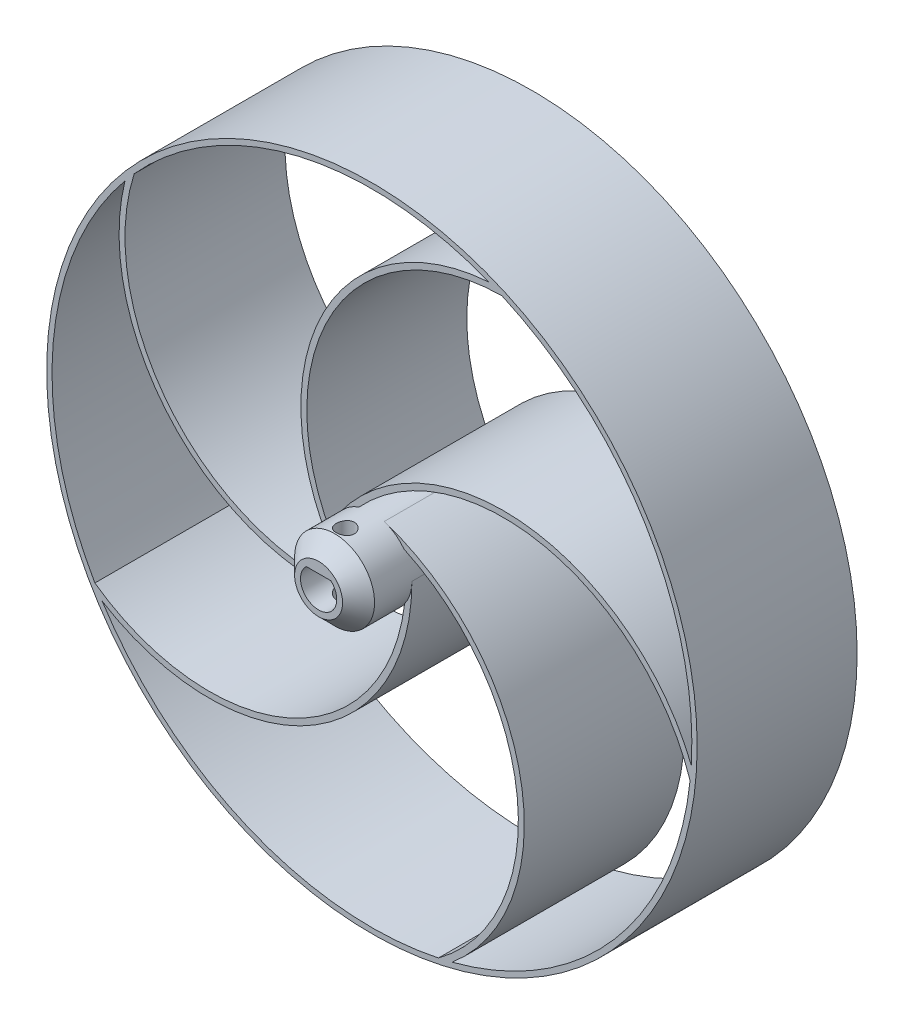
SolidWorks part; units mm, degrees
ref_plane "Front Plane" through (0, 0, 0) normal (0, 0, 1) x (1, 0, 0)
ref_plane "Top Plane" through (0, 0, 0) normal (0, 1, 0) x (1, 0, 0)
ref_plane "Right Plane" through (0, 0, 0) normal (1, 0, 0) x (0, 0, -1)
sketch "Sketch1" plane through (0, 0, 0) normal (0, 0, 1) x (1, 0, 0)
  line L0 (0, 0) -> (-30.5, 0) construction
  line L1 (-1.1522, 1.25) -> (1.1522, 1.25)
  circle A0 centre (0, 0) radius 30.5
  circle A1 centre (0, 0) radius 30
  circle A2 centre (0, 0) radius 3.75
  arc A3 (3.75, 0) -> (-25.2971, -16.1262) centre (-15.25, 0) cw
  arc A4 (3.0667, -2.1581) -> (-25.9804, -15.0007) centre (-15.25, 0) cw
  arc A5 (-1.1048, -3.5836) -> (-22.2949, 20.0734) centre (-4.7125, 14.5036) cw
  arc A6 (1.1588, -3.5665) -> (-23.1542, 19.0757) centre (-4.7125, 14.5036) cw
  arc A7 (-3.7496, -0.0566) -> (12.2014, 27.4067) centre (12.3375, 8.9637) cw
  arc A8 (-3.0338, -2.2042) -> (10.9871, 27.9157) centre (12.3375, 8.9637) cw
  arc A9 (-1.2125, 3.5486) -> (29.8357, -3.1351) centre (12.3375, -8.9637) cw
  arc A10 (-3.0338, 2.2042) -> (29.9446, -1.8229) centre (12.3375, -8.9637) cw
  arc A11 (3.0002, 2.2497) -> (6.2381, -29.3443) centre (-4.7125, -14.5036) cw
  arc A12 (1.1588, 3.5665) -> (7.5197, -29.0423) centre (-4.7125, -14.5036) cw
  arc A13 (1.1522, 1.25) -> (-1.1522, 1.25) centre (0, 0) cw
  point P9 (0, 0)
  point P10 (-15.25, 0)
  dimension "D1" = 61
  dimension "D2" = 0.5
  dimension "D3" = 7.5
  dimension "D4" = 0.5566
  dimension "D7" = 1.7
  dimension "D6" = 1.25
  dimension "D5" = 5
extrude "Boss-Extrude1" add sketch "Sketch1" along normal blind 15 contours A1 A0 | L0 A7 A1 A8 | A10 A2 A9 A1 | A7 L0 A8 A2 | L1 A13 A2 | A5 L0 A6 A2 | A2 A4 A1 A3 | A12 A2 A11 A1 | L0 A5 A1 A6 region at (-3.4656, 1.126, 0) region at (-3.8812, -0.5795, 0) region at (-4.0982, 0.3369, 0) region at (14.5975, 9.5437, 0) region at (0, 30.4137, 0) region at (-9.0413, -3.6169, 0) region at (-16.546, 0.2147, 0) region at (13.5882, -10.9337, 0) region at (-6.1989, -16.3032, 0)
sketch "Sketch2" plane through (0, 0, 15) normal (0, 0, 1) x (1, 0, 0)
  line L2 (-1.1522, 1.25) -> (1.1522, 1.25) construction
  line L3 (-1.1522, 1.25) -> (1.1522, 1.25)
  circle A0 centre (0, 0) radius 3.75
  arc A3 (-1.1522, 1.25) -> (1.1522, 1.25) centre (0, 0) ccw construction
  arc A4 (-1.1522, 1.25) -> (1.1522, 1.25) centre (0, 0) ccw
  dimension "D1" = 7.5
extrude "Boss-Extrude2" add sketch "Sketch2" along normal blind 5
sketch "Sketch3" plane through (0, 1.25, 0) normal (0, -1, 0) x (1, 0, 0)
  line L0 (1.1522, 20) -> (0, 17.5) construction
  line L1 (0, 17.5) -> (-1.1522, 20) construction
  line L3 (1.1522, 20) -> (-1.1522, 20) construction
  circle A0 centre (0, 17.5) radius 0.85
  dimension "D2" = 1.7
  dimension "D1" = 2.5
extrude "Cut-Extrude1" cut sketch "Sketch3" against normal through all and the other way through all contours A0
chamfer "Chamfer1" distance 1.5 angle 45 1 edges at (3.75, 0, 20)
